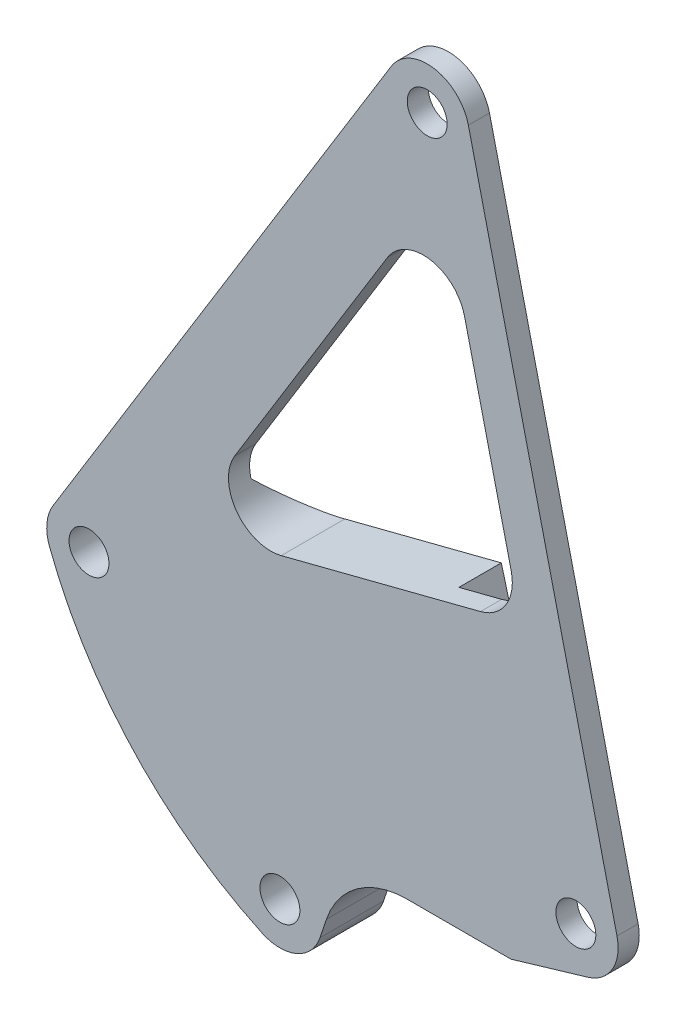
SolidWorks part; units mm, degrees
ref_plane "Front Plane" through (0, 0, 0) normal (0, 0, 1) x (1, 0, 0)
ref_plane "Top Plane" through (0, 0, 0) normal (0, 1, 0) x (1, 0, 0)
ref_plane "Right Plane" through (0, 0, 0) normal (1, 0, 0) x (0, 0, -1)
sketch "Sketch1" plane through (0, 0, 0) normal (0, 0, 1) x (1, 0, 0)
  circle A0 centre (0, 0) radius 3
  circle A1 centre (0, 0) radius 6.35
  dimension "D1" = 6
  dimension "D2" = 12.7
extrude "Boss-Extrude1" add sketch "Sketch1" along normal blind 3.1869
sketch "Sketch2" plane through (0, 0, 3.1869) normal (0, 0, 1) x (1, 0, 0)
  circle A0 centre (-28.6728, 30.8026) radius 3
  circle A1 centre (-28.6728, 30.8026) radius 6.35
  circle A2 centre (0, 0) radius 6.35 construction
  circle A3 centre (0, 0) radius 3 construction
  dimension "D1" = 28.6728
  dimension "D2" = 30.8026
extrude "Boss-Extrude2" add sketch "Sketch2" against normal blind 6.3739 separate body
sketch "Sketch3" plane through (0, 0, 0) normal (0, 0, 1) x (1, 0, 0)
  line L0 (-30.2527, 36.9529) -> (23.7075, 50.8147)
  line L1 (6.0215, -2.0158) -> (23.7075, 50.8147)
  line L2 (-28.6728, 30.8026) -> (0, 0) construction
  arc A0 (-34.6046, 28.5363) -> (-2.6848, -5.7545) centre (23.7075, 50.8147) ccw
  circle A1 centre (-28.6728, 30.8026) radius 6.35 construction
  circle A2 centre (0, 0) radius 6.35 construction
  circle A4 centre (-28.6728, 30.8026) radius 6.35
  arc A5 (-30.2527, 36.9529) -> (-34.6046, 28.5363) centre (-28.6728, 30.8026) ccw
  circle A6 centre (0, 0) radius 6.35
  arc A7 (-2.6848, -5.7545) -> (6.0215, -2.0158) centre (0, 0) ccw
  dimension "D1" = 0
  dimension "D3" = 51.9755
  dimension "D2" = 0
extrude "Boss-Extrude3" add sketch "Sketch3" along normal mid plane 6.3739 contours L0 L1 A7 A0 A5
sketch "Sketch4" plane through (0, 0, 3.1869) normal (0, 0, 1) x (1, 0, 0)
  circle A0 centre (-28.6728, 30.8026) radius 3
  circle A1 centre (0, 0) radius 3
  dimension "D1" = 6
extrude "Cut-Extrude1" cut sketch "Sketch4" against normal blind 254 and the other way through all
sketch "Sketch5" plane through (0, 0, 3.1869) normal (0, 0, 1) x (1, 0, 0)
  line L0 (23.7075, 50.8147) -> (34.7142, 9.5397)
  line L1 (34.7142, 9.5397) -> (23.7075, 9.5397)
  line L2 (23.7075, 9.5397) -> (9.89, 9.5397)
  line L3 (6.0215, -2.0158) -> (23.7075, 50.8147) construction
  line L4 (9.89, 9.5397) -> (23.7075, 50.8147)
  line L5 (34.7142, 9.5397) -> (34.7142, 50.2676) construction
  dimension "D1" = 14.931
  dimension "D2" = 41.275
extrude "Boss-Extrude4" add sketch "Sketch5" against normal blind 6.3739
fillet "Fillet1" radius 12.7 1 edges at (9.89, 9.5397, 0)
sketch "Sketch9" plane through (0, 0, 3.1869) normal (0, 0, 1) x (1, 0, 0)
  line L0 (-28.6728, 30.8026) -> (22.1272, 113.3526) construction
  line L1 (16.7192, 116.6806) -> (-34.0808, 34.1306)
  line L2 (27.5352, 110.0246) -> (-15.0246, 40.8648)
  line L3 (-30.2527, 36.9529) -> (23.7075, 50.8147) construction
  line L4 (-30.2527, 36.9529) -> (-15.0246, 40.8648)
  circle A0 centre (22.1272, 113.3526) radius 3
  circle A1 centre (-28.6728, 30.8026) radius 3 construction
  arc A2 (27.5352, 110.0246) -> (16.7192, 116.6806) centre (22.1272, 113.3526) ccw
  arc A3 (-30.2527, 36.9529) -> (-34.6046, 28.5363) centre (-28.6728, 30.8026) ccw construction
  arc A4 (-30.2527, 36.9529) -> (-34.0808, 34.1306) centre (-28.6728, 30.8026) ccw
  dimension "D1" = 50.8
  dimension "D2" = 6
  dimension "D4" = 12.7
  dimension "D3" = 82.55
extrude "Boss-Extrude8" add sketch "Sketch9" along normal blind 3.175 separate body
sketch "Sketch10" plane through (0, 0, 3.1869) normal (0, 0, 1) x (1, 0, 0)
  line L0 (34.7142, 9.5397) -> (46.2553, 12.962)
  line L1 (42.6447, 25.138) -> (31.4406, 21.8156)
  line L2 (34.7142, 9.5397) -> (23.7075, 50.8147) construction
  line L3 (31.4406, 21.8156) -> (34.7142, 9.5397)
  circle A0 centre (44.45, 19.05) radius 3
  arc A1 (46.2553, 12.962) -> (42.6447, 25.138) centre (44.45, 19.05) ccw
  dimension "D1" = 6
  dimension "D2" = 12.7
  dimension "D3" = 44.45
  dimension "D4" = 19.05
extrude "Boss-Extrude9" add sketch "Sketch10" along normal blind 3.175 separate body
sketch "Sketch11" plane through (0, 0, 3.1869) normal (0, 0, 1) x (1, 0, 0)
  circle A1 centre (0, 0) radius 3
  circle A2 centre (0, 0) radius 3
  circle A3 centre (-28.6728, 30.8026) radius 3
  circle A8 centre (-28.6728, 30.8026) radius 3
  circle M3 centre (-28.6728, 30.8026) radius 3
  circle M4 centre (0, 0) radius 3
  line M5 (23.7075, 50.8147) -> (-30.2527, 36.9529)
  arc M6 (-30.2527, 36.9529) -> (-34.6046, 28.5363) centre (-28.6728, 30.8026) ccw
  arc M7 (-34.6046, 28.5363) -> (-2.6848, -5.7545) centre (23.7075, 50.8147) ccw
  arc M8 (-2.6848, -5.7545) -> (6.0215, -2.0158) centre (0, 0) ccw
  line M9 (6.0215, -2.0158) -> (6.9881, 0.8714)
  arc M10 (6.9881, 0.8714) -> (19.0312, 9.5397) centre (19.0312, -3.1603) cw
  line M11 (19.0312, 9.5397) -> (34.7142, 9.5397)
  line M12 (34.7142, 9.5397) -> (23.7075, 50.8147)
  dimension "D1" = 0
  dimension "D2" = 0
extrude "Boss-Extrude10" add sketch "Sketch11" along normal blind 3.175 contours M12 M5 M6 M7 M8 M9 M10 M11 M4 M3 region at (0.9554, 23.7249, 3.1869)
sketch "Sketch12" plane through (0, 0, 3.1869) normal (0, 0, -1) x (-1, 0, 0)
  line L0 (-50.6292, 20.5127) -> (-28.3064, 114.8153)
  line L1 (-24.1985, 104.6024) -> (-42.985, 25.2389)
  line L2 (15.0246, 40.8648) -> (-27.5352, 110.0246) construction
  line L3 (-42.6447, 25.138) -> (-31.4406, 21.8156) construction
  line L4 (-28.3064, 114.8153) -> (-24.1985, 104.6024)
  line L5 (-50.6292, 20.5127) -> (-42.985, 25.2389)
  arc A0 (-42.6447, 25.138) -> (-46.2553, 12.962) centre (-44.45, 19.05) ccw construction
  arc A1 (-16.7192, 116.6806) -> (-27.5352, 110.0246) centre (-22.1272, 113.3526) ccw construction
  dimension "D1" = 6.35
extrude "Boss-Extrude11" add sketch "Sketch12" against normal blind 3.175
sketch "Sketch14" plane through (0, 0, 6.3619) normal (0, 0, 1) x (1, 0, 0)
  line L0 (23.7075, 50.8147) -> (36.1728, 54.017)
  line L1 (42.985, 25.2389) -> (24.1985, 104.6024) construction
  line L2 (36.1728, 54.017) -> (42.9969, 25.2315)
  line L3 (42.9969, 25.2315) -> (31.4406, 21.8156)
  line L4 (31.4406, 21.8156) -> (23.7075, 50.8147)
  line L5 (23.7075, 50.8147) -> (-15.0246, 40.8648) construction
extrude "Boss-Extrude13" add sketch "Sketch14" against normal blind 3.175
fillet "Fillet2" radius 6.35 3 edges at (-15.0246, 40.8648, 4.7744) (24.1985, 104.6024, 4.7744) (36.1728, 54.017, 4.7744)
chamfer "Chamfer1" distance 6.35 angle 45 2 edges at (-32.441, 35.9137, 3.1869) (-15.0246, 40.8648, 3.1869)
ref_plane "Plane1" through (0, 0, -5.7269) normal (0, 0, -1) x (-1, 0, 0)
